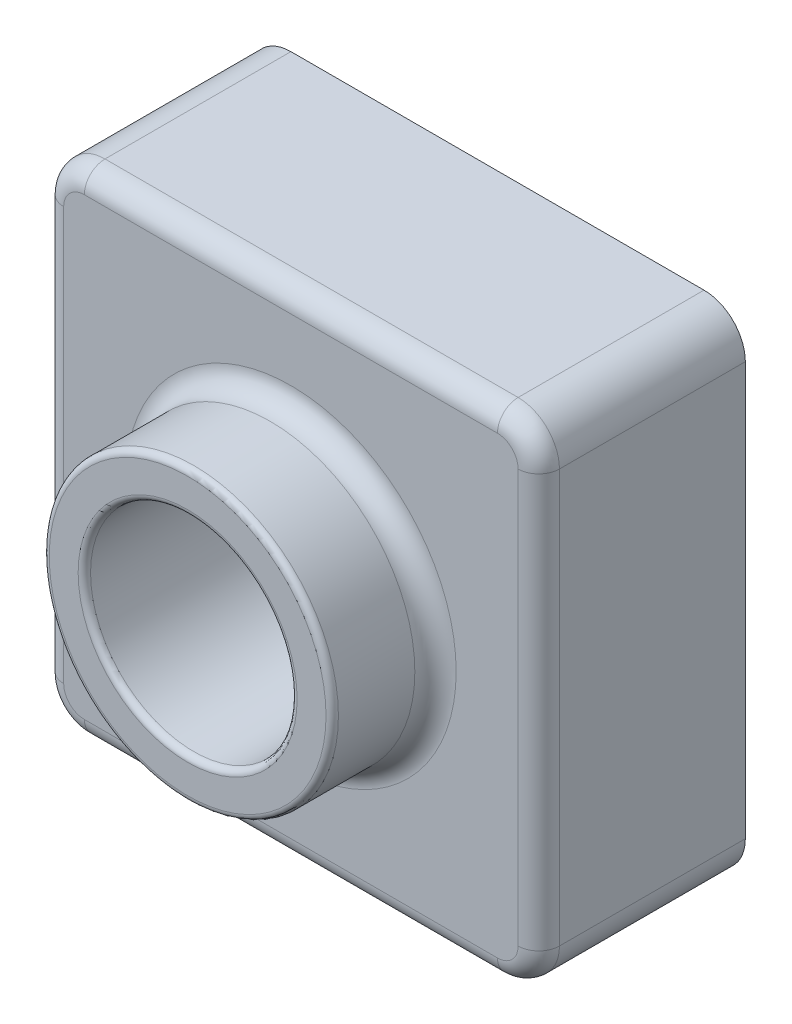
SolidWorks part; units mm, degrees
ref_plane "Front Plane" through (0, 0, 0) normal (0, 0, 1) x (1, 0, 0)
ref_plane "Top Plane" through (0, 0, 0) normal (0, 1, 0) x (1, 0, 0)
ref_plane "Right Plane" through (0, 0, 0) normal (1, 0, 0) x (0, 0, -1)
sketch "Sketch1" plane through (0, 0, 0) normal (0, 0, 1) x (1, 0, 0)
  line L1 (-60, 60) -> (60, 60)
  line L2 (-60, 60) -> (-60, -60)
  line L3 (-60, -60) -> (60, -60)
  line L4 (60, 60) -> (60, -60)
  dimension "D1" = 120
  dimension "D2" = 120
  dimension "D3" = 60
  dimension "D4" = 60
extrude "Boss-Extrude2" add sketch "Sketch1" along normal blind 50
sketch "Sketch3" plane through (0, 0, 50) normal (0, 0, 1) x (1, 0, 0)
  circle A0 centre (0, 0) radius 35
  dimension "D1" = 70
extrude "Boss-Extrude3" add sketch "Sketch3" along normal blind 25
sketch "Sketch4" plane through (0, 0, 75) normal (0, 0, 1) x (1, 0, 0)
  circle A0 centre (0, 0) radius 25
  circle A1 centre (0, 0) radius 35 construction
  dimension "D1" = 10
extrude "Cut-Extrude1" cut sketch "Sketch4" against normal through all
fillet "Fillet1" radius 5 5 edges at (35, 0, 50) (-60, 0, 50) (0, -60, 50) (60, 0, 50) (0, 60, 50)
fillet "Fillet2" radius 1.5 2 edges at (35, 0, 75) (25, 0, 75)
fillet "Fillet3" radius 10 8 edges at (-58.5355, -58.5355, 48.5355) (58.5355, -58.5355, 48.5355) (58.5355, 58.5355, 48.5355) (-58.5355, 58.5355, 48.5355) (-60, -60, 22.5) (60, -60, 22.5) (60, 60, 22.5) (-60, 60, 22.5)
shell "Shell1" thickness 2 removed face at (25, 0, 0)
